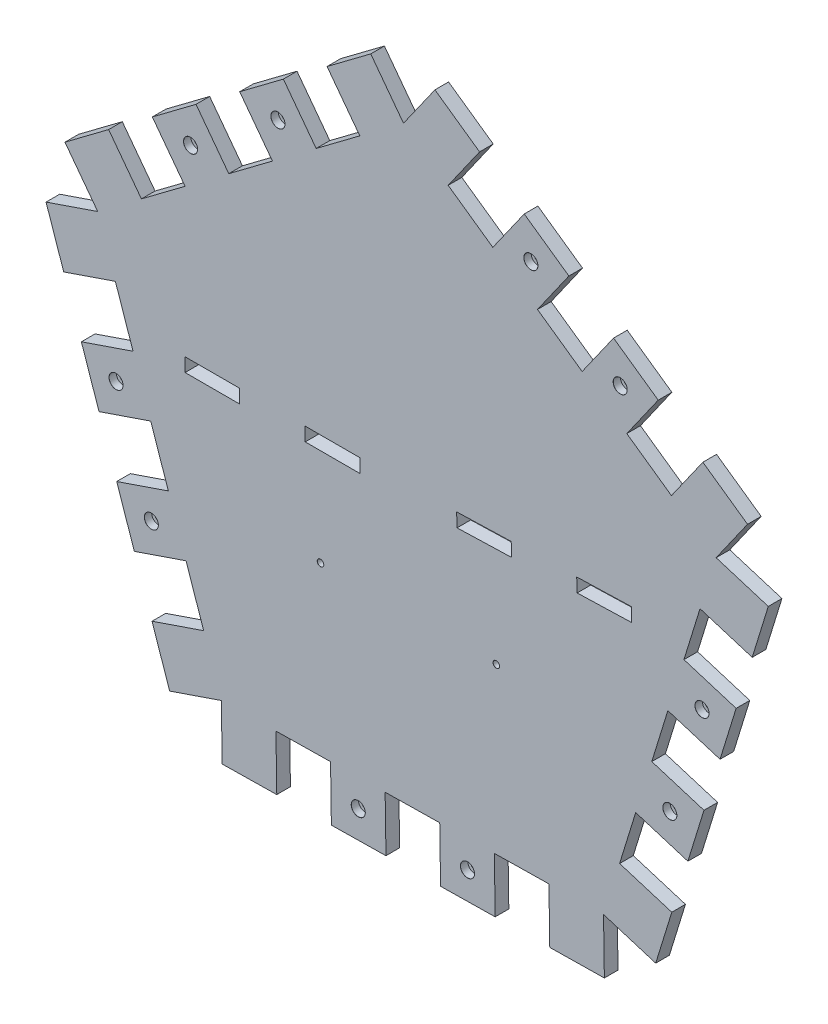
SolidWorks part; units mm, degrees
ref_plane "Front Plane" through (0, 0, 0) normal (0, 0, 1) x (1, 0, 0)
ref_plane "Top Plane" through (0, 0, 0) normal (0, 1, 0) x (1, 0, 0)
ref_plane "Right Plane" through (0, 0, 0) normal (1, 0, 0) x (0, 0, -1)
sketch "Sketch1" plane through (0, 0, 0) normal (0, 0, 1) x (1, 0, 0)
  line L0 (-144.5362, 44.5483) -> (-159.7762, 64.8683)
  line L1 (-144.5362, 44.5483) -> (-87.0321, -123.6959)
  line L2 (-87.0321, -123.6959) -> (90.7474, -120.9966)
  line L3 (90.7474, -120.9966) -> (143.1171, 48.9159)
  line L4 (143.1171, 48.9159) -> (-2.2962, 151.2283)
  line L5 (-2.2962, 151.2283) -> (-144.5362, 44.5483)
  line L6 (-159.7762, 64.8683) -> (-139.4562, 80.1083)
  line L7 (-139.4562, 80.1083) -> (-124.2162, 59.7883)
  line L8 (-124.2162, 59.7883) -> (-103.8962, 75.0283)
  line L9 (-103.8962, 75.0283) -> (-119.1362, 95.3483)
  line L10 (-119.1362, 95.3483) -> (-98.8162, 110.5883)
  line L11 (-98.8162, 110.5883) -> (-83.5762, 90.2683)
  line L12 (-83.5762, 90.2683) -> (-63.2562, 105.5083)
  line L13 (-63.2562, 105.5083) -> (-78.4962, 125.8283)
  line L14 (-78.4962, 125.8283) -> (-58.1762, 141.0683)
  line L15 (-58.1762, 141.0683) -> (-42.9362, 120.7483)
  line L16 (-22.6162, 135.9883) -> (-37.8562, 156.3083)
  line L17 (-37.8562, 156.3083) -> (-17.5362, 171.5483)
  line L18 (-17.5362, 171.5483) -> (-2.2962, 151.2283)
  line L19 (-2.2962, 151.2283) -> (12.3198, 172.0016)
  line L20 (12.3198, 172.0016) -> (33.0932, 157.3856)
  line L21 (33.0932, 157.3856) -> (18.4771, 136.6122)
  line L22 (39.2504, 121.9962) -> (53.8665, 142.7695)
  line L23 (53.8665, 142.7695) -> (74.6398, 128.1535)
  line L24 (74.6398, 128.1535) -> (60.0238, 107.3801)
  line L25 (95.4131, 113.5374) -> (116.1865, 98.9214)
  line L26 (80.7971, 92.7641) -> (95.4131, 113.5374)
  line L27 (116.1865, 98.9214) -> (101.5704, 78.148)
  line L28 (122.3437, 63.532) -> (136.9598, 84.3053)
  line L29 (136.9598, 84.3053) -> (157.7331, 69.6893)
  line L30 (157.7331, 69.6893) -> (143.1171, 48.9159)
  line L31 (143.1171, 48.9159) -> (167.3903, 41.4346)
  line L32 (167.3903, 41.4346) -> (159.9089, 17.1613)
  line L33 (159.9089, 17.1613) -> (135.6357, 24.6427)
  line L34 (128.1543, 0.3695) -> (152.4275, -7.1119)
  line L35 (152.4275, -7.1119) -> (144.9462, -31.3851)
  line L36 (144.9462, -31.3851) -> (120.6729, -23.9037)
  line L37 (137.4648, -55.6583) -> (129.9834, -79.9315)
  line L38 (113.1916, -48.1769) -> (137.4648, -55.6583)
  line L39 (129.9834, -79.9315) -> (105.7102, -72.4501)
  line L40 (98.2288, -96.7234) -> (122.502, -104.2047)
  line L41 (122.502, -104.2047) -> (115.0206, -128.4779)
  line L42 (115.0206, -128.4779) -> (90.7474, -120.9966)
  line L43 (90.7474, -120.9966) -> (91.1331, -146.3936)
  line L44 (91.1331, -146.3936) -> (65.736, -146.7793)
  line L45 (65.736, -146.7793) -> (65.3504, -121.3822)
  line L46 (39.9533, -121.7678) -> (40.3389, -147.1649)
  line L47 (40.3389, -147.1649) -> (14.9418, -147.5505)
  line L48 (14.9418, -147.5505) -> (14.5562, -122.1534)
  line L49 (-10.4552, -147.9361) -> (-35.8523, -148.3218)
  line L50 (-10.8409, -122.5391) -> (-10.4552, -147.9361)
  line L51 (-35.8523, -148.3218) -> (-36.2379, -122.9247)
  line L52 (-61.635, -123.3103) -> (-61.2494, -148.7074)
  line L53 (-61.2494, -148.7074) -> (-86.6465, -149.093)
  line L54 (-86.6465, -149.093) -> (-87.0321, -123.6959)
  line L55 (-87.0321, -123.6959) -> (-111.067, -131.9108)
  line L56 (-111.067, -131.9108) -> (-119.2818, -107.8759)
  line L57 (-119.2818, -107.8759) -> (-95.247, -99.661)
  line L58 (-103.4618, -75.6262) -> (-127.4967, -83.841)
  line L59 (-127.4967, -83.841) -> (-135.7116, -59.8061)
  line L60 (-135.7116, -59.8061) -> (-111.6767, -51.5913)
  line L61 (-143.9265, -35.7713) -> (-152.1413, -11.7364)
  line L62 (-119.8916, -27.5564) -> (-143.9265, -35.7713)
  line L63 (-152.1413, -11.7364) -> (-128.1065, -3.5215)
  line L64 (-136.3213, 20.5134) -> (-160.3562, 12.2985)
  line L65 (-160.3562, 12.2985) -> (-168.5711, 36.3334)
  line L66 (-168.5711, 36.3334) -> (-144.5362, 44.5483)
  line L67 (-2.2962, 151.2283) -> (1.8577, -122.3463) construction
  line L68 (-22.6162, 0) -> (-22.6162, 6.35)
  line L69 (-22.6162, 6.35) -> (-48.0162, 6.35)
  line L70 (-48.0162, 6.35) -> (-48.0162, 0)
  line L71 (-48.0162, 0) -> (-22.6162, 0)
  line L72 (-78.4962, 6.35) -> (-103.8962, 6.35)
  line L73 (-103.8962, 6.35) -> (-103.8962, 0)
  line L74 (-103.8962, 0) -> (-78.4962, 0)
  line L75 (-78.4962, 0) -> (-78.4962, 6.35)
  line L76 (47.8013, 7.8049) -> (47.9941, 1.4578)
  line L77 (22.6058, 0.6866) -> (22.413, 7.0337)
  line L78 (47.9941, 1.4578) -> (22.6058, 0.6866)
  line L79 (22.413, 7.0337) -> (47.8013, 7.8049)
  line L80 (103.8483, 3.1543) -> (78.46, 2.3832)
  line L81 (103.6555, 9.5014) -> (103.8483, 3.1543)
  line L82 (78.2672, 8.7303) -> (103.6555, 9.5014)
  line L83 (78.46, 2.3832) -> (78.2672, 8.7303)
  circle A0 centre (0, 0) radius 122.3604 construction
  dimension "D1" = 25.4
  dimension "D2" = 177.8
  dimension "D3" = 25.4
  dimension "D4" = 25.4
  dimension "D5" = 25.4
  dimension "D6" = 25.4
  dimension "D7" = 25.4
  dimension "D8" = 25.4
  dimension "D9" = 25.4
  dimension "D10" = 25.4
  dimension "D11" = 25.4
  dimension "D12" = 25.4
  dimension "D13" = 20.32
  dimension "D15" = 6.35
  dimension "D16" = 6.35
  dimension "D17" = 25.4
  dimension "D18" = 25.4
  dimension "D19" = 30.48
  dimension "D14" = 5
extrude "Boss-Extrude3" add sketch "Sketch1" along normal blind 6.35 contours L11 L10 L9 L5 | L7 L6 L0 L5 | L66 L65 L64 L1 | L63 L61 L62 L1 | L60 L59 L58 L1 | L57 L56 L55 L1 | L54 L53 L52 L2 | L51 L49 L50 L2 | L48 L47 L46 L2 | L42 L41 L40 L3 | L39 L37 L38 L3 | L45 L44 L43 L2 | L36 L35 L34 L3 | L33 L32 L31 L3 | L30 L29 L28 L4 | L24 L23 L22 L4 | L21 L20 L19 L4 | L4 L5 L1 L2 L3 L75 L74 L73 L72 L71 L70 L69 L68 L77 L79 L76 L78 | L27 L25 L26 L4 | L18 L17 L16 L5 region at (0.0008, -0.0496, 0) region at (-141.9962, 62.3283, 0) region at (-152.4462, 28.4234, 0) region at (-136.0165, -19.6464, 0) region at (-101.3562, 92.8083, 0) region at (-119.5867, -67.7161, 0) region at (-103.157, -115.7859, 0) region at (-20.0762, 153.7683, 0) region at (-74.1407, -136.2017, 0) region at (15.3985, 154.3069, 0) region at (-23.3466, -135.4304, 0) region at (56.9451, 125.0748, 0) region at (27.4476, -134.6592, 0) region at (98.4918, 95.8427, 0) region at (78.2417, -133.8879, 0) region at (140.0384, 66.6106, 0) region at (106.6247, -112.6007, 0) region at (151.513, 33.0386, 0) region at (121.5875, -64.0542, 0) region at (136.5502, -15.5078, 0)
extrude "Boss-Extrude5" add sketch "Sketch1<6>" along normal blind 6.35 contours L15 L14 L13 L5 region at (-60.7162, 123.2883, 0)
sketch "Sketch1<6>" plane through (0, 0, 0) normal (0, 0, 1) x (1, 0, 0) same geometry as "Sketch1"
sketch "Sketch9" plane through (0, 0, 6.35) normal (0, 0, 1) x (1, 0, 0)
  line L0 (-108.9762, 102.9683) -> (-93.7362, 82.6483) construction
  line L1 (-119.1362, 95.3483) -> (-98.8162, 110.5883) construction
  line L2 (-2.2962, 151.2283) -> (-144.5362, 44.5483) construction
  line L3 (-68.3362, 133.4483) -> (-53.0962, 113.1283) construction
  line L4 (-78.4962, 125.8283) -> (-58.1762, 141.0683) construction
  point P12 (-101.3562, 92.8083)
  point P14 (-60.7162, 123.2883)
  dimension "D1" = 90
  dimension "D2" = 90
hole_wizard "CBORE for M3 Hex Socket Head Cap Screw1" positions "Sketch9" profile "Sketch10" counterbore size "M3" standard "ISO" end condition through all
sketch "Sketch10" plane through (-60.7162, 123.2883, 6.35) normal (1, 0, 0) x (0, -1, 0)
  line L0 (0, 0) -> (0, 6.35)
  line L1 (0, 6.35) -> (1.7, 6.35)
  line L3 (1.7, 6.35) -> (1.7, 3.4)
  line L4 (3.25, 3.4) -> (1.7, 3.4)
  line L5 (3.25, 3.4) -> (3.25, 0.025)
  line L6 (3.25, 0.025) -> (3.275, 0)
  line L7 (3.275, 0) -> (0, 0)
  line L8 (-3.25, 0.025) -> (-3.275, 0) construction
  line L11 (0, -6.35) -> (0, 107.95) construction
  dimension "Thru Hole Dia." = 3.4
  dimension "Thru Hole Depth" = 6.35
  dimension "C'Bore Dia." = 6.5
  dimension "C'Bore Depth" = 3.4
  dimension "Near C'Sink Dia." = 6.55
  dimension "Near C'Sink Angle" = 90
ref_axis "Axis1" through (0, 0, 0) along (0, 0, 1)
pattern_circular "CirPattern1" count 5 every 72 about axis through (0, 0, 0) along (0, 0, 1) of "CBORE for M3 Hex Socket Head Cap Screw1"
sketch "Sketch11" plane through (0, 0, 6.35) normal (0, 0, 1) x (1, 0, 0)
  line L0 (-48.0162, -39.116) -> (47.9958, -39.116)
  line L1 (47.9958, -39.116) -> (47.9958, -89.916)
  line L2 (47.9958, -89.916) -> (-48.0162, -89.916)
  line L3 (-48.0162, -89.916) -> (-48.0162, -39.116)
  circle A0 centre (-40.9042, -45.212) radius 1.4986
  circle A1 centre (40.8838, -45.212) radius 1.4986
  dimension "D5" = 2.9972
  dimension "D6" = 2.9972
  dimension "D9" = 6.096
  dimension "D1" = 50.8
  dimension "D2" = 96.012
  dimension "D3" = 39.116
  dimension "D4" = 55.4456
  dimension "D7" = 7.112
  dimension "D8" = 7.112
  dimension "D10" = 6.096
hole_wizard "Ø3.0mm Dowel Hole1" positions "Sketch12" profile "Sketch13" hole size "Ø3.0" standard "ANSI Metric" end condition through all
sketch "Sketch12" plane through (0, 0, 6.35) normal (0, 0, 1) x (1, 0, 0)
  point P0 (-40.9042, -45.212)
  point P3 (40.8838, -45.212)
sketch "Sketch13" plane through (-40.9042, -45.212, 6.35) normal (1, 0, 0) x (0, -1, 0)
  line L0 (0, 0) -> (0, 6.35)
  line L1 (0, 6.35) -> (1.5, 6.35)
  line L2 (1.5, 6.35) -> (1.5, 0.025)
  line L3 (1.5, 0.025) -> (1.525, 0)
  line L5 (1.525, 0) -> (0, 0)
  line L6 (-1.5, 0.025) -> (-1.525, 0) construction
  line L11 (0, -6.35) -> (0, 107.95) construction
  dimension "Thru Hole Dia." = 3
  dimension "Thru Hole Depth" = 6.35
  dimension "Near C'Sink Dia." = 3.05
  dimension "Near C'Sink Angle" = 90
